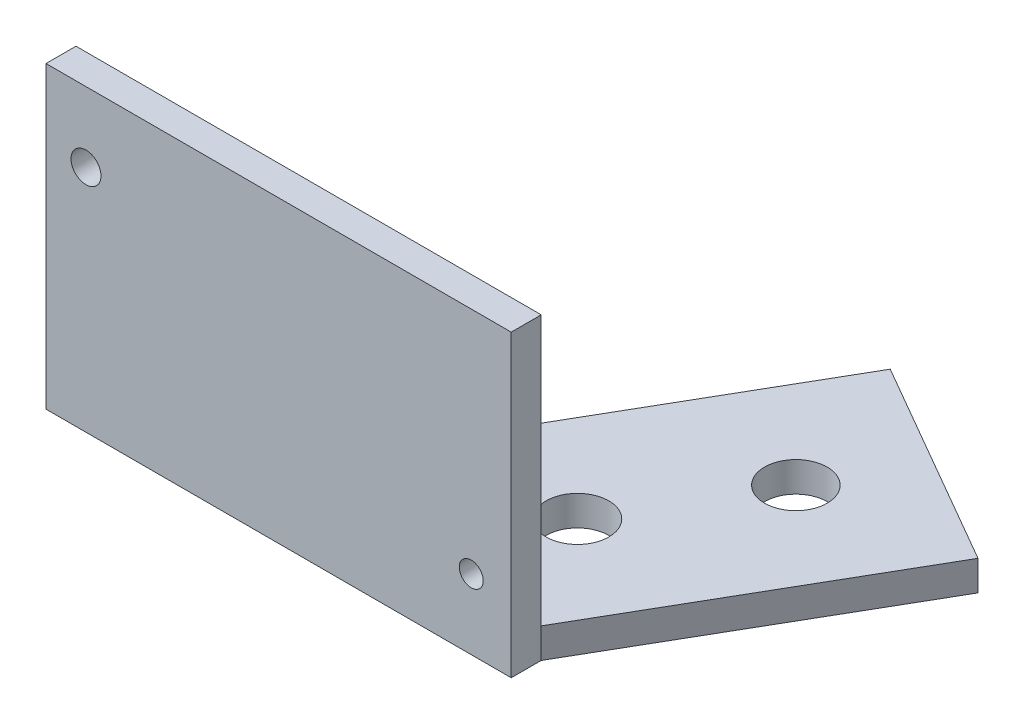
SolidWorks part; units mm, degrees
ref_plane "Front Plane" through (0, 0, 0) normal (0, 0, 1) x (1, 0, 0)
ref_plane "Top Plane" through (0, 0, 0) normal (0, 1, 0) x (1, 0, 0)
ref_plane "Right Plane" through (0, 0, 0) normal (1, 0, 0) x (0, 0, -1)
sketch "Sketch1" plane through (0, 0, 0) normal (0, 0, 1) x (1, 0, 0)
  line L1 (0, 0) -> (33.782, 0) construction
  line L2 (0, 0) -> (0, 19.812) construction
  line L3 (0, 19.812) -> (33.782, 19.812) construction
  line L4 (33.782, 0) -> (33.782, 19.812) construction
  line L5 (-1.5875, -1.5875) -> (35.3695, -1.5875)
  line L6 (-1.5875, -1.5875) -> (-1.5875, 19.812)
  line L7 (-1.5875, 19.812) -> (35.3695, 19.812)
  line L8 (35.3695, -1.5875) -> (35.3695, 19.812)
  circle A0 centre (1.5875, 14.2558) radius 1.1906
  circle A1 centre (32.1945, 1.5875) radius 0.9525
  dimension "D3" = 2.3813
  dimension "D4" = 1.905
  dimension "D5" = 1.5875
  dimension "D6" = 1.5875
  dimension "D7" = 1.5875
  dimension "D8" = 5.5562
  dimension "D9" = 3.175
  dimension "D11" = 3.175
  dimension "D12" = 5.5562
  dimension "D1" = 19.812
  dimension "D2" = 33.782
  dimension "D10" = 3.175
extrude "Boss-Extrude1" add sketch "Sketch1" along normal blind 2.3813
sketch "Sketch2" plane through (0, -1.5875, 0) normal (0, -1, 0) x (1, 0, 0)
  line L8 (-1.5875, 0) -> (35.3695, 0) construction
  line L9 (-1.5875, 2.3813) -> (35.3695, 2.3813)
  line L10 (-1.5875, 2.3813) -> (-1.5875, 0)
  line L12 (35.3695, 2.3813) -> (35.3695, 0)
  line L15 (48.0695, -21.997) -> (31.5717, -31.522)
  line L17 (48.0695, -21.997) -> (35.3695, 0)
  line L19 (31.5717, -31.522) -> (13.3725, 0)
  line L20 (13.3725, 0) -> (-1.5875, 0)
  dimension "D1" = 19.05
  dimension "D2" = 25.4
  dimension "D3" = 60
extrude "Boss-Extrude3" add sketch "Sketch2" along normal blind 2.3813
sketch "Sketch4" plane through (0, -1.5875, 0) normal (0, 1, 0) x (1, 0, 0)
  line L0 (39.8206, 26.7595) -> (35.801, 19.7973) construction
  line L2 (35.801, 19.7973) -> (29.451, 8.7988) construction
  line L3 (29.451, 8.7988) -> (24.371, 0) construction
  line L5 (48.0695, 21.997) -> (31.5717, 31.522) construction
  line L6 (35.3695, 0) -> (13.3725, 0) construction
  circle A0 centre (35.801, 19.7973) radius 2.4892
  circle A1 centre (29.451, 8.7988) radius 2.4892
  point P10 (24.371, 0)
  point P15 (39.8206, 26.7595)
  dimension "D1" = 4.9784
  dimension "D2" = 12.7
  dimension "D3" = 10.16
extrude "Cut-Extrude2" cut sketch "Sketch4" against normal up to next
